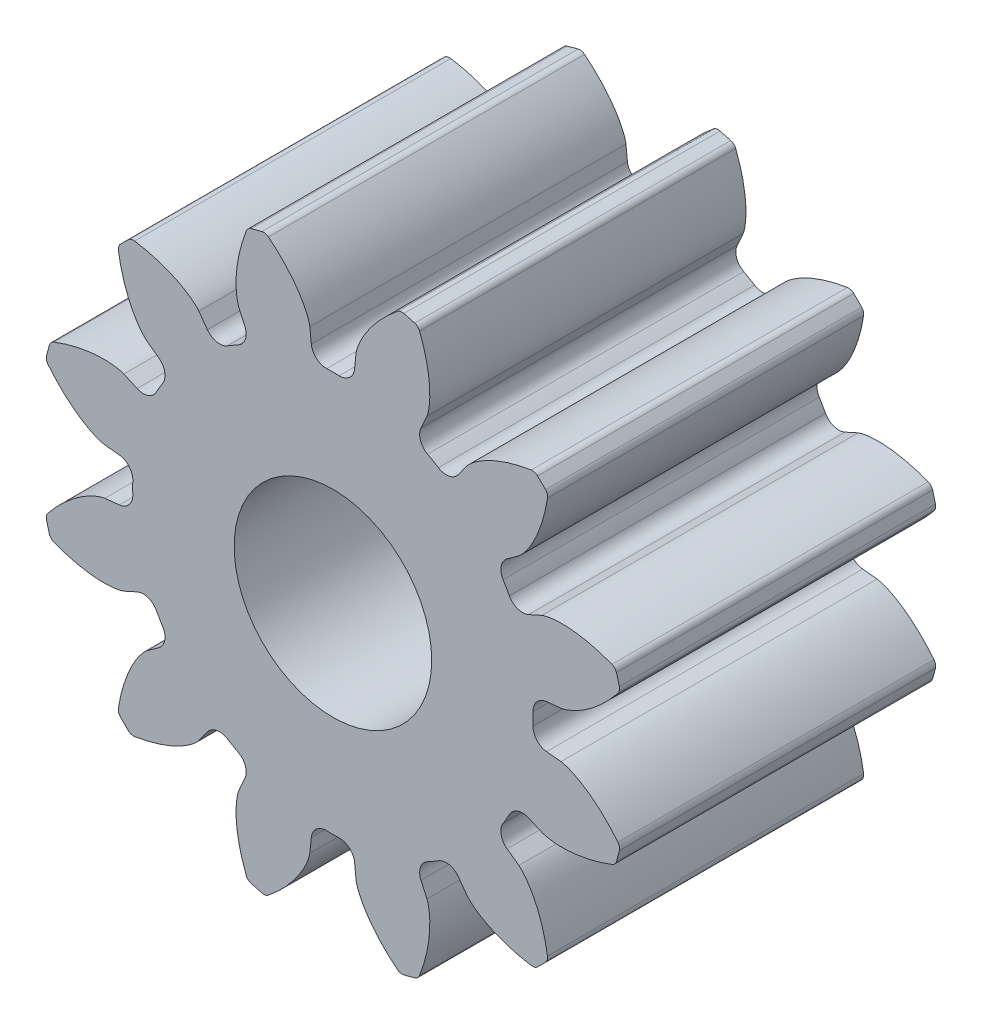
SolidWorks part; units mm, degrees
material "DELRIN"
ref_plane "Front" through (0, 0, 0) normal (0, 0, 1) x (1, 0, 0)
ref_plane "Top" through (0, 0, 0) normal (0, 1, 0) x (1, 0, 0)
ref_plane "Right" through (0, 0, 0) normal (1, 0, 0) x (0, 0, -1)
sketch "Sketch1" plane through (0, 0, 0) normal (0, 0, 1) x (1, 0, 0)
  circle A0 centre (0, 0) radius 11.8533
  dimension "OutsideDiameter" = 23.7067
extrude "Boss-Extrude1" add sketch "Sketch1" along normal blind 12.7
sketch "Sketch3" plane through (0, 0, 0) normal (0, 0, 1) x (1, 0, 0)
  line L0 (0, 0) -> (43.7181, 0) construction
  line L2 (0, 0) -> (-0.8104, 8.0024) construction
  line L3 (0, 0) -> (0.8104, 8.0024) construction
  line L4 (0.8104, 8.0024) -> (0.9277, 9.1612) construction
  line L5 (0, 0) -> (0, 61.276) construction
  line L6 (-0.8104, 8.0024) -> (-0.9277, 9.1612) construction
  circle A0 centre (0, 0) radius 11.8533 construction
  circle A1 centre (0, 0) radius 10.16 construction
  circle A2 centre (0, 0) radius 9.2081 construction
  arc A3 (0.8104, 8.0024) -> (-0.8104, 8.0024) centre (0, 0) ccw construction
  arc A5 (2.7064, 11.5402) -> (-2.7064, 11.5402) centre (0, 0) ccw
  spline S0 degree 4 poles (-0.9277, 9.1612) (-0.9283, 9.1657) (-0.93, 9.1781) (-0.9342, 9.2015) (-0.9423, 9.2394) (-0.9545, 9.2874) (-0.9726, 9.3489) (-0.9967, 9.4206) (-1.026, 9.4987) (-1.0611, 9.5826) (-1.0988, 9.6655) (-1.1389, 9.7473) (-1.1812, 9.8279) (-1.235, 9.9246) (-1.3032, 10.0389) (-1.3882, 10.1702) (-1.4906, 10.3162) (-1.6015, 10.4617) (-1.7158, 10.602) (-1.8371, 10.7404) (-1.9586, 10.8719) (-2.0907, 11.0047) (-2.2156, 11.1255) (-2.3617, 11.2564) (-2.4815, 11.3607) (-2.6459, 11.4936) (-2.7449, 11.5706) (-2.863, 11.659) (-2.9166, 11.6974) (-2.9495, 11.721) knots 0 0 0 0 0 0.005377 0.015084 0.028532 0.04661 0.064855 0.092111 0.119476 0.146842 0.174209 0.201575 0.228941 0.256307 0.307035 0.361767 0.4165 0.471232 0.525964 0.580697 0.635429 0.690161 0.744894 0.799626 0.854358 0.909091 0.954545 1 1 1 1 1 construction
  spline S1 degree 4 poles (-0.9277, 9.1612) (-0.9283, 9.1657) (-0.93, 9.1781) (-0.9342, 9.2015) (-0.9423, 9.2394) (-0.9545, 9.2874) (-0.9726, 9.3489) (-0.9967, 9.4206) (-1.026, 9.4987) (-1.0611, 9.5826) (-1.0988, 9.6655) (-1.1389, 9.7473) (-1.1812, 9.8279) (-1.235, 9.9246) (-1.3032, 10.0389) (-1.3882, 10.1702) (-1.4906, 10.3162) (-1.6015, 10.4617) (-1.7158, 10.602) (-1.8371, 10.7404) (-1.9586, 10.8719) (-2.0907, 11.0047) (-2.2156, 11.1255) (-2.3617, 11.2564) (-2.4815, 11.3607) (-2.6102, 11.4648) (-2.6737, 11.5149) (-2.7064, 11.5402) knots 0 0 0 0 0 0.005377 0.015084 0.028532 0.04661 0.064855 0.092111 0.119476 0.146842 0.174209 0.201575 0.228941 0.256307 0.307035 0.361767 0.4165 0.471232 0.525964 0.580697 0.635429 0.690161 0.744894 0.799626 0.854358 0.909091 0.909091 0.909091 0.909091 0.909091
  spline S2 degree 4 poles (0.9277, 9.1612) (0.9283, 9.1657) (0.93, 9.1781) (0.9342, 9.2015) (0.9423, 9.2394) (0.9545, 9.2874) (0.9726, 9.3489) (0.9967, 9.4206) (1.026, 9.4987) (1.0611, 9.5826) (1.0988, 9.6655) (1.1389, 9.7473) (1.1812, 9.8279) (1.235, 9.9246) (1.3032, 10.0389) (1.3882, 10.1702) (1.4906, 10.3162) (1.6015, 10.4617) (1.7158, 10.602) (1.8371, 10.7404) (1.9586, 10.8719) (2.0907, 11.0047) (2.2156, 11.1255) (2.3617, 11.2564) (2.4815, 11.3607) (2.6459, 11.4936) (2.7449, 11.5706) (2.863, 11.659) (2.9166, 11.6974) (2.9495, 11.721) knots 0 0 0 0 0 0.005377 0.015084 0.028532 0.04661 0.064855 0.092111 0.119476 0.146842 0.174209 0.201575 0.228941 0.256307 0.307035 0.361767 0.4165 0.471232 0.525964 0.580697 0.635429 0.690161 0.744894 0.799626 0.854358 0.909091 0.954545 1 1 1 1 1 construction
  spline S3 degree 4 poles (0.9277, 9.1612) (0.9283, 9.1657) (0.93, 9.1781) (0.9342, 9.2015) (0.9423, 9.2394) (0.9545, 9.2874) (0.9726, 9.3489) (0.9967, 9.4206) (1.026, 9.4987) (1.0611, 9.5826) (1.0988, 9.6655) (1.1389, 9.7473) (1.1812, 9.8279) (1.235, 9.9246) (1.3032, 10.0389) (1.3882, 10.1702) (1.4906, 10.3162) (1.6015, 10.4617) (1.7158, 10.602) (1.8371, 10.7404) (1.9586, 10.8719) (2.0907, 11.0047) (2.2156, 11.1255) (2.3617, 11.2564) (2.4815, 11.3607) (2.6102, 11.4648) (2.6737, 11.5149) (2.7064, 11.5402) knots 0 0 0 0 0 0.005377 0.015084 0.028532 0.04661 0.064855 0.092111 0.119476 0.146842 0.174209 0.201575 0.228941 0.256307 0.307035 0.361767 0.4165 0.471232 0.525964 0.580697 0.635429 0.690161 0.744894 0.799626 0.854358 0.909091 0.909091 0.909091 0.909091 0.909091
  point P0 (0, 8.0433)
  dimension "OutsideDiameter" = 23.7067
  dimension "PitchCircle" = 20.32
  dimension "BaseCircle" = 18.4162
  dimension "DedendumCircle" = 16.0867
sketch "DCLTBC" plane through (0, 0, 0) normal (0, 0, 1) x (1, 0, 0)
  line L0 (0, 0) -> (41.04, 0) construction
  line L1 (-0.8104, 8.0024) -> (-0.9277, 9.1612) construction
  line L2 (0.8104, 8.0024) -> (0.9277, 9.1612) construction
  line L3 (-0.8104, 8.0024) -> (-0.9277, 9.1612)
  line L4 (0.8104, 8.0024) -> (0.9277, 9.1612)
  line L5 (0, 0) -> (0, 104.9356) construction
  circle A0 centre (0, 0) radius 11.8533
  circle A1 centre (0, 0) radius 10.16 construction
  circle A2 centre (0, 0) radius 9.2081 construction
  arc A3 (0.8104, 8.0024) -> (-0.8104, 8.0024) centre (0, 0) ccw construction
  arc A4 (0.8104, 8.0024) -> (-0.8104, 8.0024) centre (0, 0) ccw
  spline S0 degree 4 poles (-994.4739, -104.1267) (-14.2903, 6.4195) (-1.0522, 8.2498) (-0.8415, 8.7688) (-0.9423, 9.2394) (-0.9545, 9.2874) (-0.9726, 9.3489) (-0.9967, 9.4206) (-1.026, 9.4987) (-1.0611, 9.5826) (-1.0988, 9.6655) (-1.1389, 9.7473) (-1.1812, 9.8279) (-1.235, 9.9246) (-1.3032, 10.0389) (-1.3882, 10.1702) (-1.4906, 10.3162) (-1.6015, 10.4617) (-1.7158, 10.602) (-1.8371, 10.7404) (-1.9586, 10.8719) (-2.0907, 11.0047) (-2.2156, 11.1255) (-2.3617, 11.2564) (-2.9486, 11.7679) (-5.0034, 13.2442) (18.8088, -5.4292) (-793.4231, 623.6867) knots -0.531769 -0.531769 -0.531769 -0.531769 -0.531769 0.005377 0.015084 0.028532 0.04661 0.064855 0.092111 0.119476 0.146842 0.174209 0.201575 0.228941 0.256307 0.307035 0.361767 0.4165 0.471232 0.525964 0.580697 0.635429 0.690161 0.744894 0.799626 0.854358 1.763028 1.763028 1.763028 1.763028 1.763028 only from (-0.9277, 9.1612) to (-2.7064, 11.5402) construction
  spline S1 degree 4 poles (994.4739, -104.1267) (14.2903, 6.4195) (1.0522, 8.2498) (0.8415, 8.7688) (0.9423, 9.2394) (0.9545, 9.2874) (0.9726, 9.3489) (0.9967, 9.4206) (1.026, 9.4987) (1.0611, 9.5826) (1.0988, 9.6655) (1.1389, 9.7473) (1.1812, 9.8279) (1.235, 9.9246) (1.3032, 10.0389) (1.3882, 10.1702) (1.4906, 10.3162) (1.6015, 10.4617) (1.7158, 10.602) (1.8371, 10.7404) (1.9586, 10.8719) (2.0907, 11.0047) (2.2156, 11.1255) (2.3617, 11.2564) (2.9486, 11.7679) (5.0034, 13.2442) (-18.8088, -5.4292) (793.4231, 623.6867) knots -0.531769 -0.531769 -0.531769 -0.531769 -0.531769 0.005377 0.015084 0.028532 0.04661 0.064855 0.092111 0.119476 0.146842 0.174209 0.201575 0.228941 0.256307 0.307035 0.361767 0.4165 0.471232 0.525964 0.580697 0.635429 0.690161 0.744894 0.799626 0.854358 1.763028 1.763028 1.763028 1.763028 1.763028 only from (0.9277, 9.1612) to (2.7064, 11.5402) construction
  spline S2 degree 4 poles (-0.9277, 9.1612) (-0.9283, 9.1657) (-0.93, 9.1781) (-0.9342, 9.2015) (-0.9423, 9.2394) (-0.9545, 9.2874) (-0.9726, 9.3489) (-0.9967, 9.4206) (-1.026, 9.4987) (-1.0611, 9.5826) (-1.0988, 9.6655) (-1.1389, 9.7473) (-1.1812, 9.8279) (-1.235, 9.9246) (-1.3032, 10.0389) (-1.3882, 10.1702) (-1.4906, 10.3162) (-1.6015, 10.4617) (-1.7158, 10.602) (-1.8371, 10.7404) (-1.9586, 10.8719) (-2.0907, 11.0047) (-2.2156, 11.1255) (-2.3617, 11.2564) (-2.4815, 11.3607) (-2.6102, 11.4648) (-2.6737, 11.5149) (-2.7064, 11.5402) knots 0 0 0 0 0 0.005377 0.015084 0.028532 0.04661 0.064855 0.092111 0.119476 0.146842 0.174209 0.201575 0.228941 0.256307 0.307035 0.361767 0.4165 0.471232 0.525964 0.580697 0.635429 0.690161 0.744894 0.799626 0.854358 0.909091 0.909091 0.909091 0.909091 0.909091
  spline S3 degree 4 poles (0.9277, 9.1612) (0.9283, 9.1657) (0.93, 9.1781) (0.9342, 9.2015) (0.9423, 9.2394) (0.9545, 9.2874) (0.9726, 9.3489) (0.9967, 9.4206) (1.026, 9.4987) (1.0611, 9.5826) (1.0988, 9.6655) (1.1389, 9.7473) (1.1812, 9.8279) (1.235, 9.9246) (1.3032, 10.0389) (1.3882, 10.1702) (1.4906, 10.3162) (1.6015, 10.4617) (1.7158, 10.602) (1.8371, 10.7404) (1.9586, 10.8719) (2.0907, 11.0047) (2.2156, 11.1255) (2.3617, 11.2564) (2.4815, 11.3607) (2.6102, 11.4648) (2.6737, 11.5149) (2.7064, 11.5402) knots 0 0 0 0 0 0.005377 0.015084 0.028532 0.04661 0.064855 0.092111 0.119476 0.146842 0.174209 0.201575 0.228941 0.256307 0.307035 0.361767 0.4165 0.471232 0.525964 0.580697 0.635429 0.690161 0.744894 0.799626 0.854358 0.909091 0.909091 0.909091 0.909091 0.909091
  dimension "OutsideDiameter" = 23.7067
  dimension "PitchCircle" = 20.32
  dimension "BaseCircle" = 18.4162
extrude "Cut-Extrude-DCLTBC" cut sketch "DCLTBC" along normal through all contours L4 S3 A0 S2 L3 A4 region at (0, 10.3262, 0)
fillet "Fillet-Tip-DCLTBC" radius 0.3011 2 edges at (2.7064, 11.5402, 6.35) (-2.7064, 11.5402, 6.35)
fillet "Fillet-Root-DCLTBC" radius 0.6022 2 edges at (-0.8104, 8.0024, 6.35) (0.8104, 8.0024, 6.35)
pattern_circular "CirPattern-DCLTBC" count 12 over 360 about axis through (0, 0, 12.7) along (0, 0, 1) of "Cut-Extrude-DCLTBC", "Fillet-Tip-DCLTBC", "Fillet-Root-DCLTBC"
sketch "DCGTBC" [suppressed] plane through (0, 0, 0) normal (0, 0, 1) x (1, 0, 0)
  line L0 (0, 0) -> (41.04, 0) construction
  line L1 (-60.6226, 5.3038) -> (0, 0) construction
  line L2 (0, 0) -> (60.6226, 5.3038) construction
  line L3 (0, 0) -> (-16.5124, 0)
  line L5 (0, 0) -> (0, 104.9356) construction
  circle A0 centre (0, 0) radius 65.6167
  circle A1 centre (0, 0) radius 63.5 construction
  circle A2 centre (0, 0) radius 57.5505 construction
  arc A3 (-0.231, 60.8537) -> (0.231, 60.8537) centre (0, 0) ccw construction
  arc A11 (60.6226, 5.3038) -> (-60.6226, 5.3038) centre (0, 0) ccw
  spline S4 degree 4 poles (999.5281, 37.5164) (15.9379, 54.4029) (0.0707, 55.4419) (-0.2895, 56.6024) (-0.2066, 57.7767) (-0.1929, 57.9173) (-0.1708, 58.0988) (-0.1393, 58.3123) (-0.0988, 58.5468) (-0.0484, 58.8015) (0.0074, 59.0552) (0.0683, 59.3079) (0.1336, 59.5593) (0.2182, 59.8633) (0.3273, 60.227) (0.4659, 60.6511) (0.6363, 61.1305) (0.824, 61.6174) (1.0202, 62.0951) (1.2316, 62.5758) (1.4455, 63.0396) (1.6812, 63.5192) (1.9056, 63.9609) (2.1719, 64.4533) (3.0421, 66.0274) (5.6872, 70.2084) (-15.0429, 35.5301) (520.7458, 920.9699) knots -0.449335 -0.449335 -0.449335 -0.449335 -0.449335 0.005377 0.015084 0.028532 0.04661 0.064855 0.092111 0.119476 0.146842 0.174209 0.201575 0.228941 0.256307 0.307035 0.361767 0.4165 0.471232 0.525964 0.580697 0.635429 0.690161 0.744894 0.799626 0.854358 1.559054 1.559054 1.559054 1.559054 1.559054 only from (-0.2184, 57.5501) to (2.8092, 65.5565) construction
  spline S5 degree 4 poles (-999.5281, 37.5164) (-15.9379, 54.4029) (-0.0707, 55.4419) (0.2895, 56.6024) (0.2066, 57.7767) (0.1929, 57.9173) (0.1708, 58.0988) (0.1393, 58.3123) (0.0988, 58.5468) (0.0484, 58.8015) (-0.0074, 59.0552) (-0.0683, 59.3079) (-0.1336, 59.5593) (-0.2182, 59.8633) (-0.3273, 60.227) (-0.4659, 60.6511) (-0.6363, 61.1305) (-0.824, 61.6174) (-1.0202, 62.0951) (-1.2316, 62.5758) (-1.4455, 63.0396) (-1.6812, 63.5192) (-1.9056, 63.9609) (-2.1719, 64.4533) (-3.0421, 66.0274) (-5.6872, 70.2084) (15.0429, 35.5301) (-520.7458, 920.9699) knots -0.449335 -0.449335 -0.449335 -0.449335 -0.449335 0.005377 0.015084 0.028532 0.04661 0.064855 0.092111 0.119476 0.146842 0.174209 0.201575 0.228941 0.256307 0.307035 0.361767 0.4165 0.471232 0.525964 0.580697 0.635429 0.690161 0.744894 0.799626 0.854358 1.559054 1.559054 1.559054 1.559054 1.559054 only from (0.2184, 57.5501) to (-2.8092, 65.5565) construction
  spline S6 degree 4 poles (-0.2184, 57.5501) (-0.2183, 57.5629) (-0.2176, 57.5987) (-0.2144, 57.6663) (-0.2066, 57.7767) (-0.1929, 57.9173) (-0.1708, 58.0988) (-0.1393, 58.3123) (-0.0988, 58.5468) (-0.0484, 58.8015) (0.0074, 59.0552) (0.0683, 59.3079) (0.1336, 59.5593) (0.2182, 59.8633) (0.3273, 60.227) (0.4659, 60.6511) (0.6363, 61.1305) (0.824, 61.6174) (1.0202, 62.0951) (1.2316, 62.5758) (1.4455, 63.0396) (1.6812, 63.5192) (1.9056, 63.9609) (2.1719, 64.4533) (2.3911, 64.8499) (2.63, 65.2574) (2.7481, 65.4554) (2.8092, 65.5565) knots 0 0 0 0 0 0.005377 0.015084 0.028532 0.04661 0.064855 0.092111 0.119476 0.146842 0.174209 0.201575 0.228941 0.256307 0.307035 0.361767 0.4165 0.471232 0.525964 0.580697 0.635429 0.690161 0.744894 0.799626 0.854358 0.909091 0.909091 0.909091 0.909091 0.909091
  spline S7 degree 4 poles (0.2184, 57.5501) (0.2183, 57.5629) (0.2176, 57.5987) (0.2144, 57.6663) (0.2066, 57.7767) (0.1929, 57.9173) (0.1708, 58.0988) (0.1393, 58.3123) (0.0988, 58.5468) (0.0484, 58.8015) (-0.0074, 59.0552) (-0.0683, 59.3079) (-0.1336, 59.5593) (-0.2182, 59.8633) (-0.3273, 60.227) (-0.4659, 60.6511) (-0.6363, 61.1305) (-0.824, 61.6174) (-1.0202, 62.0951) (-1.2316, 62.5758) (-1.4455, 63.0396) (-1.6812, 63.5192) (-1.9056, 63.9609) (-2.1719, 64.4533) (-2.3911, 64.8499) (-2.63, 65.2574) (-2.7481, 65.4554) (-2.8092, 65.5565) knots 0 0 0 0 0 0.005377 0.015084 0.028532 0.04661 0.064855 0.092111 0.119476 0.146842 0.174209 0.201575 0.228941 0.256307 0.307035 0.361767 0.4165 0.471232 0.525964 0.580697 0.635429 0.690161 0.744894 0.799626 0.854358 0.909091 0.909091 0.909091 0.909091 0.909091
  dimension "D1" = 5
  dimension "D2" = 5
  dimension "OutsideDiameter" = 23.7067
  dimension "PitchCircle" = 20.32
  dimension "BaseCircle" = 18.4162
extrude "Cut-Extrude-DCGTBC" [suppressed] cut sketch "DCGTBC" along normal through all
fillet "Fillet-Tip-DCGTBC" [suppressed] radius 0.3011
pattern_circular "CirPattern-DCGTBC" [suppressed] count 12 over 360 of bodies 112
sketch "Sketch8" plane through (0, 0, 0) normal (0, 0, 1) x (1, 0, 0)
  line L0 (18.125, -4.6) -> (21.725, -4.6)
  circle A2 centre (19.925, -7) radius 3
  circle A3 centre (0, 0) radius 3.9688
  dimension "D1" = 6
  dimension "13mm" = 7.9375
  dimension "D3" = 3.6
extrude "Cut-Extrude5" cut sketch "Sketch8" along normal blind 25.4 contours A3 region at (0, 0, 0)
equation "\"DiametralPitch\"= 15'Diametral Pitch"
equation "\"NumTeeth\"= 12'Number of Teeth"
equation "\"PressureAngle\"= 25deg'Pressure Angle"
equation "\"Addendum\"= 1 / \"DiametralPitch\"'Addendum"
equation "\"Dedendum\"= 1.25 / \"DiametralPitch\"'Dedendum"
equation "\"WorkingDepth\"= 2 / \"DiametralPitch\"'Working Depth - here for REF (Not used in building model)"
equation "\"WholeDepth\"= 2.25 / \"DiametralPitch\"'Whole Depth - here for REF (Not used in building model)"
equation "\"Clearance\"= .25 / \"DiametralPitch\"'Clearance"
equation "\"CircularPitch\"= pi / \"DiametralPitch\"'Circular Pitch - here for REF (Not used in building model)"
equation "\"PitchCircle\"= \"NumTeeth\" / \"DiametralPitch\"'Pitch Circle - or - Pitch Diameter"
equation "\"OutsideDiameter\"= ( \"NumTeeth\" + 2 ) / \"DiametralPitch\"'Outside Diameter"
equation "\"Fillet_Root\"= \"Clearance\" * cos ( \"PressureAngle\" ) * tan ( ( 90 + \"PressureAngle\" ) / 2 ) 'Fillet Root"
equation "\"AddendumCircle\"= \"PitchCircle\" + ( 2 * \"Addendum\" )'Addendum Circle - or - Addendum Diameter"
equation "\"DedendumCircle\"= \"PitchCircle\" - ( 2 * \"Dedendum\" )'Dedendum Circle - or - Dedendum Diameter"
equation "\"BaseCircle\"= \"PitchCircle\" * cos ( \"PressureAngle\" )'Base Circle - Base Diameter"
equation "\"PitchAngle\"= 360deg / \"NumTeeth\"'Pitch Angle"
equation "\"Alpha\"= sqr ( \"PitchCircle\" ^ 2 - \"BaseCircle\" ^ 2 ) / \"BaseCircle\" * 180 / PI - \"PressureAngle\"'Alpha - Used for Calculating Beta"
equation "\"Beta\"= ( \"PitchAngle\" / 4 - ( \"Alpha\" - 90 ) )'Beta - Used in definition of the parameters for the parametric equation driven curve"
equation "\"Gamma\"= ( \"PitchAngle\" / 4 - ( \"Alpha\" + 90 ) )'Gamma - Used in definition of the parameters for the parametric equation driven curve"
equation "\"Phi\"= sqr ( ( \"AddendumCircle\" / 2 ) ^ 2 - ( \"BaseCircle\" / 2 ) ^ 2 ) / ( \"BaseCircle\" / 2 )'Phi - Used in definition of the parameters for the parametric equation driven curve"
equation "\"DCGTBC\"= iif ( \"DedendumCircle\" > \"BaseCircle\" , \"unsuppressed\" , \"suppressed\" )'if Dedendum Circle IS GREATER THAN BaseCircle THEN UnsuppressORSuppress FEATURE"
equation "\"DCLTBC\"= iif ( \"DedendumCircle\" - .002 > \"BaseCircle\" , \"suppressed\" , \"unsuppressed\" )'if Dedendum Circle - .002 IS GREATER THAN BaseCircle THEN SuppressORUnsuppress FEATURE"
equation "\"Cut-Extrude-DCGTBC\"= iif ( \"DedendumCircle\" > \"BaseCircle\" , \"unsuppressed\" , \"suppressed\" )'if Dedendum Circle IS GREATER THAN BaseCircle THEN UnsuppressORSuppress FEATURE"
equation "\"Cut-Extrude-DCLTBC\"= iif ( \"DedendumCircle\" - .002 > \"BaseCircle\" , \"suppressed\" , \"unsuppressed\" )'if Dedendum Circle - .002 IS GREATER THAN BaseCircle THEN SuppressORUnsuppress FEATURE"
equation "\"CirPattern-DCGTBC\"= iif ( \"DedendumCircle\" > \"BaseCircle\" , \"unsuppressed\" , \"suppressed\" )'if Dedendum Circle IS GREATER THAN BaseCircle THEN UnsuppressORSuppress FEATURE"
equation "\"CirPattern-DCLTBC\"= iif ( \"DedendumCircle\" - .002 > \"BaseCircle\" , \"suppressed\" , \"unsuppressed\" )'if Dedendum Circle - .002 IS GREATER THAN BaseCircle THEN SuppressORUnsuppress FEATURE"
equation "\"Fillet-Tip-DCGTBC\"= iif ( \"DedendumCircle\" > \"BaseCircle\" , \"unsuppressed\" , \"suppressed\" )'if Dedendum Circle IS GREATER THAN BaseCircle THEN UnsuppressORSuppress FEATURE"
equation "\"Fillet-Tip-DCLTBC\"= iif ( \"DedendumCircle\" - .002 > \"BaseCircle\" , \"suppressed\" , \"unsuppressed\" )'if Dedendum Circle - .002 IS GREATER THAN BaseCircle THEN SuppressORUnsuppress FEATURE"
equation "\"Fillet-Root-DCLTBC\"= iif ( \"DedendumCircle\" - .002 > \"BaseCircle\" , \"suppressed\" , \"unsuppressed\" )'if Dedendum Circle - .002 IS GREATER THAN BaseCircle THEN SuppressORUnsuppress FEATURE"
equation "\"D1@CirPattern-DCGTBC\"= \"NumTeeth\"'Number of Teeth"
equation "\"D1@CirPattern-DCLTBC\"= \"NumTeeth\"'Number of Teeth"
equation "\"D1@Fillet-Tip-DCGTBC\"= \"Fillet_Root\" / 2 'Tip Rad For Large No of Teeth"
equation "\"D1@Fillet-Tip-DCLTBC\"=\"Fillet_Root\" / 2'Tip Rad For Small No of Teeth"
equation "\"D1@Fillet-Root-DCLTBC\"= \"Fillet_Root\"'Fillet Root"
